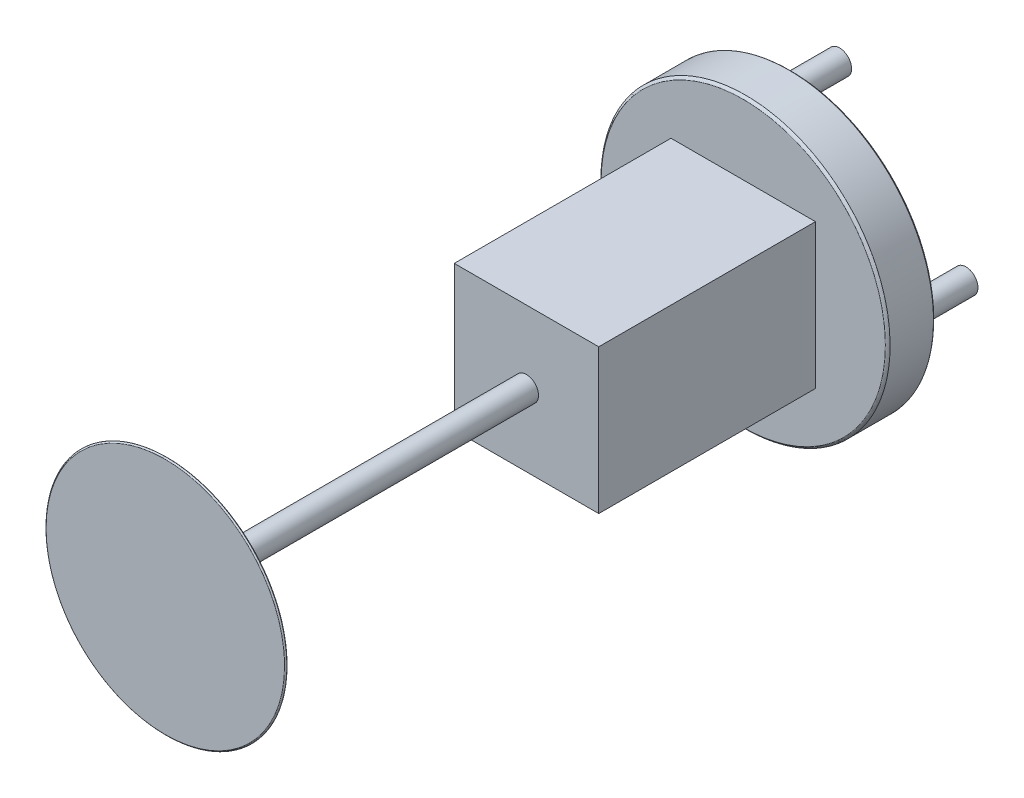
SolidWorks part; units mm, degrees
ref_plane "Front Plane" through (0, 0, 0) normal (0, 0, 1) x (1, 0, 0)
ref_plane "Top Plane" through (0, 0, 0) normal (0, 1, 0) x (1, 0, 0)
ref_plane "Right Plane" through (0, 0, 0) normal (1, 0, 0) x (0, 0, -1)
sketch "Sketch1" plane through (0, 0, 0) normal (0, 0, 1) x (1, 0, 0)
  circle A0 centre (0, 0) radius 60
  dimension "D1" = 120
extrude "Boss-Extrude1" add sketch "Sketch1" along normal blind 20
sketch "Sketch2" plane through (0, 0, 0) normal (0, 0, -1) x (-1, 0, 0)
  circle A0 centre (0, 52.5) radius 5
  circle A1 centre (52.5, 0) radius 5
  circle A2 centre (0, -52.5) radius 5
  circle A3 centre (-52.5, 0) radius 5
  dimension "D1" = 10
  dimension "D2" = 52.5
  dimension "D3" = 4
fillet "Fillet1" radius 1 1 edges at (60, 0, 0) conic rho 0.1
fillet "Fillet2" radius 1 1 edges at (60, 0, 20) conic rho 0.1
extrude "Boss-Extrude2" add sketch "Sketch2" along normal blind 20
sketch "Sketch3" plane through (0, 0, 20) normal (0, 0, 1) x (1, 0, 0)
  line L1 (-30, 30) -> (30, 30)
  line L2 (-30, 30) -> (-30, -30)
  line L3 (-30, -30) -> (30, -30)
  line L4 (30, 30) -> (30, -30)
  line L5 (-30, 30) -> (30, -30) construction
  line L6 (-30, -30) -> (30, 30) construction
  point P0 (0, 0)
  dimension "D1" = 60
  dimension "D2" = 60
extrude "Boss-Extrude3" add sketch "Sketch3" along normal blind 90
sketch "Sketch4" plane through (0, 0, 110) normal (0, 0, 1) x (1, 0, 0)
  circle A0 centre (0, 0) radius 5
  dimension "D1" = 10
extrude "Boss-Extrude4" add sketch "Sketch4" along normal blind 150
sketch "Sketch5" plane through (0, 0, 260) normal (0, 0, 1) x (1, 0, 0)
  circle A0 centre (0, 0) radius 50
  dimension "D1" = 100
extrude "Boss-Extrude5" add sketch "Sketch5" against normal blind 1
fillet "Fillet3" radius 0.5 2 edges at (50, 0, 260) (50, 0, 259) conic rho 0.1
